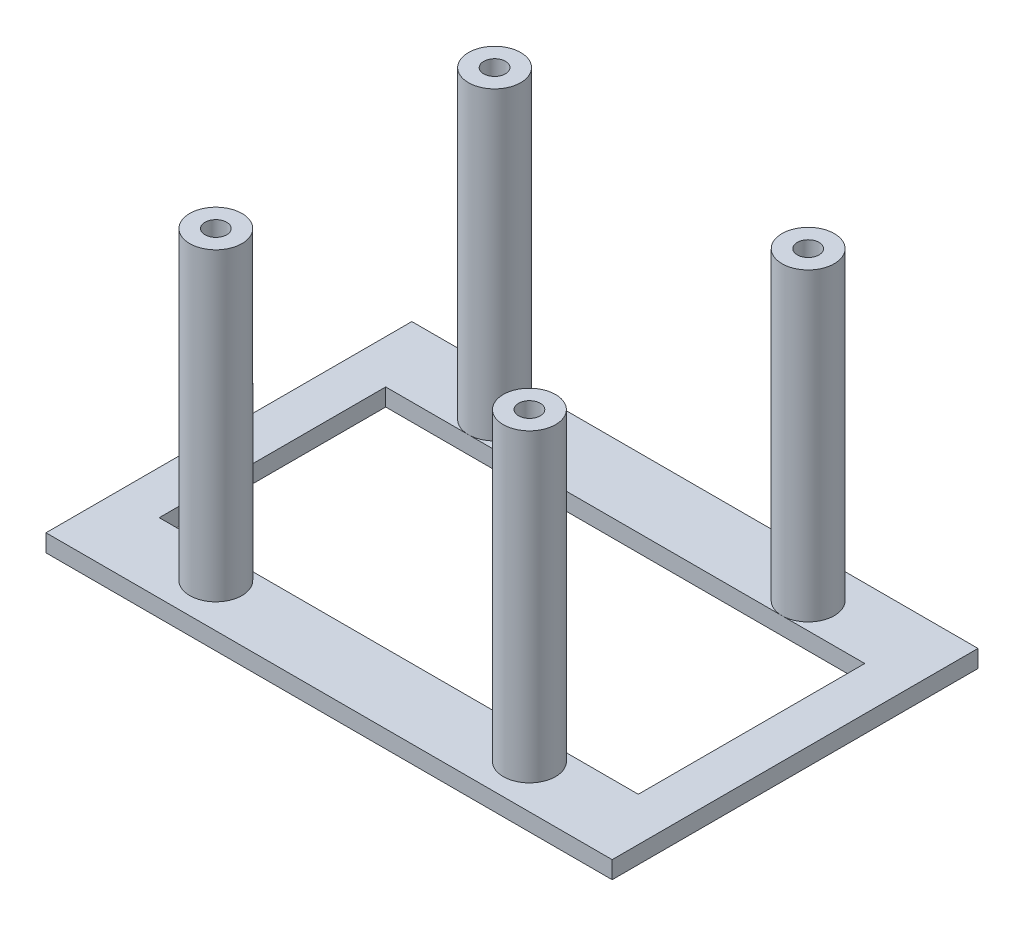
SolidWorks part; units mm, degrees
ref_plane "Front Plane" through (0, 0, 0) normal (0, 0, 1) x (1, 0, 0)
ref_plane "Top Plane" through (0, 0, 0) normal (0, 1, 0) x (1, 0, 0)
ref_plane "Right Plane" through (0, 0, 0) normal (1, 0, 0) x (0, 0, -1)
sketch "Sketch1" plane through (0, 0, 0) normal (0, 1, 0) x (1, 0, 0)
  line L1 (-32.5, -21) -> (32.5, -21)
  line L2 (-32.5, -21) -> (-32.5, 21)
  line L3 (-32.5, 21) -> (32.5, 21)
  line L4 (32.5, -21) -> (32.5, 21)
  line L5 (-32.5, -21) -> (32.5, 21) construction
  line L6 (-32.5, 21) -> (32.5, -21) construction
  line L7 (-18, -16) -> (18, -16) construction
  line L8 (-18, -16) -> (-18, 16) construction
  line L9 (-18, 16) -> (18, 16) construction
  line L10 (18, -16) -> (18, 16) construction
  line L11 (-18, -16) -> (18, 16) construction
  line L12 (-18, 16) -> (18, -16) construction
  line L13 (-27.5, -13) -> (27.5, -13)
  line L14 (-27.5, -13) -> (-27.5, 13)
  line L15 (-27.5, 13) -> (27.5, 13)
  line L16 (27.5, -13) -> (27.5, 13)
  line L17 (-27.5, -13) -> (27.5, 13) construction
  line L18 (-27.5, 13) -> (27.5, -13) construction
  circle A0 centre (-18, 16) radius 3
  circle A1 centre (-18, 16) radius 1.25
  circle A2 centre (18, 16) radius 3
  circle A3 centre (18, 16) radius 1.25
  circle A4 centre (18, -16) radius 3
  circle A5 centre (18, -16) radius 1.25
  circle A6 centre (-18, -16) radius 3
  circle A7 centre (-18, -16) radius 1.25
  point P0 (0, 0)
  point P6 (0, 0)
  point P11 (0, 0)
  dimension "D3" = 6
  dimension "D4" = 2.5
  dimension "D1" = 32
  dimension "D2" = 36
  dimension "D5" = 26
  dimension "D6" = 55
  dimension "D7" = 5
  dimension "D8" = 5
extrude "Boss-Extrude2" add sketch "Sketch1" against normal blind 2 contours L1 L4 L3 L2 L13 A6 L14 L15 A0 A2 L16 A4 | A0 A1 | A1 | A2 A3 | A4 A5 | A5 | A6 A7 | A7 | A3 region at (-31.7261, 0, 0) region at (-20.0613, 0, -18.0613) region at (15.9387, 0, -18.0613) region at (20.0613, 0, 13.9387) region at (-15.9387, 0, 13.9387) region at (-18, 0, -16) region at (18, 0, 16) region at (-18, 0, 16)
extrude "Boss-Extrude3" add sketch "Sketch1<3>" along normal blind 35 contours A0 A1 | A1 | A2 A3 | A3 | A4 A5 | A7 | A6 A7 | A5 region at (-20.0613, 0, -18.0613) region at (15.9387, 0, -18.0613) region at (20.0613, 0, 13.9387) region at (-15.9387, 0, 13.9387) region at (-18, 0, -16) region at (18, 0, -16) region at (18, 0, 16) region at (-18, 0, 16)
sketch "Sketch1<3>" plane through (0, 0, 0) normal (0, 1, 0) x (1, 0, 0) same geometry as "Sketch1"
extrude "Cut-Extrude1" cut sketch "Sketch1<4>" against normal blind 11 from surface contours A1 | A3 | A5 | A7 starting at face at (-18, 35, 19)
sketch "Sketch1<4>" plane through (0, 0, 0) normal (0, 1, 0) x (1, 0, 0) same geometry as "Sketch1"
